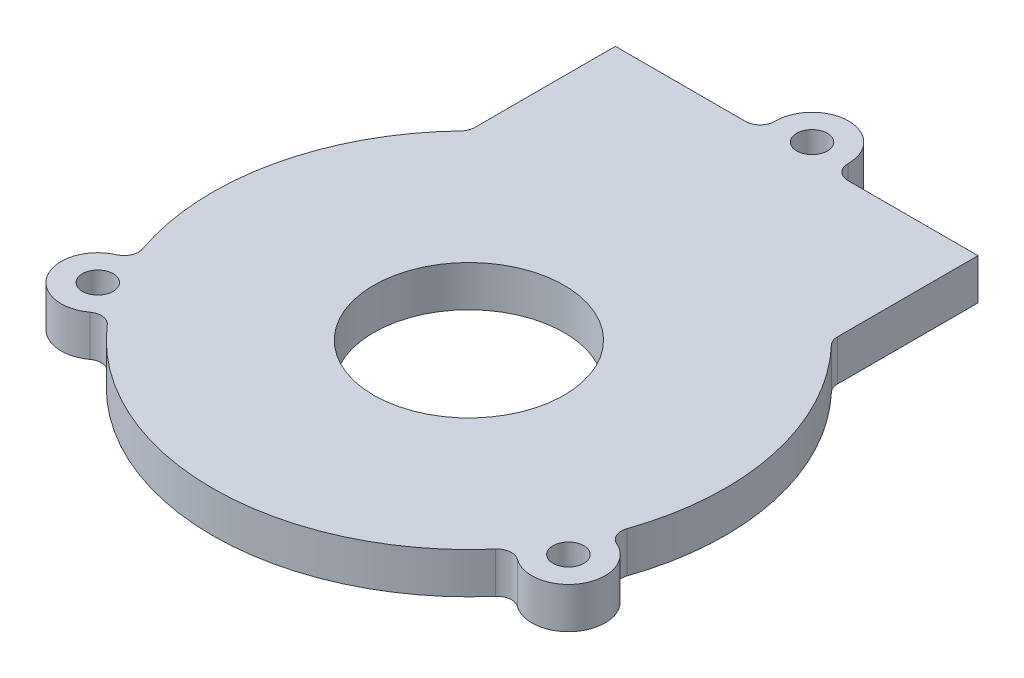
SolidWorks part; units mm, degrees
ref_plane "Front Plane" through (0, 0, 0) normal (0, 0, 1) x (1, 0, 0)
ref_plane "Top Plane" through (0, 0, 0) normal (0, 1, 0) x (1, 0, 0)
ref_plane "Right Plane" through (0, 0, 0) normal (1, 0, 0) x (0, 0, -1)
sketch "Sketch13" plane through (0, 0, 0) normal (0, 1, 0) x (1, 0, 0)
  circle A0 centre (0, 0) radius 35
extrude "Boss-Extrude3" add sketch "Sketch13" along normal blind 5.588
sketch "Sketch14" plane through (0, 5.588, 0) normal (0, 1, 0) x (1, 0, 0)
  line L0 (-24.7478, 24.7497) -> (24.7477, 24.7498)
  line L1 (-24.7478, 24.7497) -> (-24.7479, 44.7452)
  line L2 (24.7477, 24.7498) -> (24.7476, 44.7454)
  line L3 (-24.7479, 44.7452) -> (24.7476, 44.7454)
  line L4 (0, 0) -> (60.4611, -34.8658) construction
  line L5 (0, 0) -> (-56.6044, -32.6614) construction
  line L7 (-3.939, 44.1714) -> (-8.8985, 44.1714)
  line L8 (-3.939, 44.1714) -> (-3.939, 47.547)
  line L9 (-3.939, 47.547) -> (-8.8985, 47.547)
  line L10 (-8.8985, 44.1714) -> (-8.8985, 47.547)
  arc A0 (0, 35) -> (-24.7478, 24.7497) centre (0, 0) ccw construction
  circle A1 centre (0, 0) radius 35 construction
  arc A2 (0, 35) -> (-30.3109, -17.4999) centre (0, 0) ccw construction
  arc A3 (0, 35) -> (30.3118, -17.4984) centre (0, 0) ccw
  arc A4 (0, 35) -> (24.7477, 24.7498) centre (0, 0) ccw construction
  circle A5 centre (32.1365, -18.5413) radius 2.1017
  circle A6 centre (32.1365, -18.5413) radius 4.9951
  circle A7 centre (-32.1465, -18.5162) radius 2.0981
  circle A8 centre (-32.1465, -18.5162) radius 4.9995
extrude "Boss-Extrude4" add sketch "Sketch14" against normal up to surface (5.588 mm away) contours L0 L1 L3 L2 up to face at (0, 0, 35)
sketch "Sketch15" plane through (0, 5.588, 0) normal (0, 1, 0) x (1, 0, 0)
  line L0 (0, 0) -> (0, 62.3966) construction
  line L1 (-0.0001, 44.7453) -> (0, 46.8414) construction
  line L2 (-24.7479, 44.7452) -> (24.7476, 44.7454) construction
  circle A0 centre (0, 46.8414) radius 2.0961
  circle A1 centre (0, 46.8414) radius 4.996
extrude "Boss-Extrude11" add sketch "Sketch15" against normal up to surface (5.588 mm away) contours A1 | A0 up to face at (-0.0001, 0, -19.8101)
extrude "Boss-Extrude12" add sketch "Sketch14<6>" against normal up to surface (5.588 mm away) contours A6 up to face at (0, 0, -29.3038)
sketch "Sketch14<6>" plane through (0, 5.588, 0) normal (0, 1, 0) x (1, 0, 0) same geometry as "Sketch14"
extrude "Boss-Extrude14" add sketch "Sketch14<8>" against normal up to surface (5.588 mm away) contours L0 A5 region at (32.1365, 5.588, 18.5413) up to face at (5.9749, 0, -21.2696)
sketch "Sketch14<8>" plane through (0, 5.588, 0) normal (0, 1, 0) x (1, 0, 0) same geometry as "Sketch14"
hole_wizard "Ø4.2 (4.2) Diameter Hole1" positions "Sketch22" profile "Sketch23" hole size "Ø4.2" standard "ANSI Metric" end condition through all
sketch "Sketch22" plane through (0, 5.588, 0) normal (0, 1, 0) x (1, 0, 0)
  point P0 (32.1248, -18.5356)
sketch "Sketch23" plane through (32.1248, 5.588, 18.5356) normal (1, 0, 0) x (0, 0, 1)
  line L0 (0, 0) -> (0, 5.588)
  line L1 (0, 5.588) -> (2.1, 5.588)
  line L2 (2.1, 5.588) -> (2.1, 0)
  line L5 (2.1, 0) -> (0, 0)
  line L11 (0, -6.35) -> (0, 107.95) construction
  dimension "Thru Hole Dia." = 4.2
  dimension "Thru Hole Depth" = 5.588
extrude "Boss-Extrude15" add sketch "Sketch14<11>" against normal up to surface (5.588 mm away) contours A8 up to face at (32.1248, 0, 20.6356)
sketch "Sketch14<11>" plane through (0, 5.588, 0) normal (0, 1, 0) x (1, 0, 0) same geometry as "Sketch14"
hole_wizard "Ø4.2 (4.2) Diameter Hole2" positions "Sketch26" profile "Sketch27" hole size "Ø4.2" standard "ANSI Metric" end condition through all
sketch "Sketch26" plane through (0, 5.588, 0) normal (0, 1, 0) x (1, 0, 0)
  point P0 (-32.148, -18.5088)
  point P2 (-32.148, -18.5088)
sketch "Sketch27" plane through (-32.148, 5.588, 18.5088) normal (1, 0, 0) x (0, 0, 1)
  line L0 (0, 0) -> (0, 5.588)
  line L1 (0, 5.588) -> (2.1, 5.588)
  line L2 (2.1, 5.588) -> (2.1, 0)
  line L5 (2.1, 0) -> (0, 0)
  line L11 (0, -6.35) -> (0, 107.95) construction
  dimension "Thru Hole Dia." = 4.2
  dimension "Thru Hole Depth" = 5.588
fillet "Fillet4" radius 2 1 edges at (-24.7478, 2.794, -24.7497)
fillet "Fillet6" radius 2 1 edges at (-32.2839, 2.794, 13.5185)
fillet "Fillet7" radius 2 1 edges at (-27.8924, 2.794, 21.1427)
fillet "Fillet8" radius 2 1 edges at (27.8812, 2.794, 21.1574)
fillet "Fillet9" radius 2 1 edges at (32.2715, 2.794, 13.548)
fillet "Fillet10" radius 2 1 edges at (24.7477, 2.794, -24.7498)
fillet "Fillet11" radius 2 1 edges at (4.535, 2.794, -44.7453)
fillet "Fillet12" radius 2 1 edges at (-4.535, 2.794, -44.7453)
sketch "Sketch28" plane through (0, 5.588, 0) normal (0, 1, 0) x (1, 0, 0)
  circle A0 centre (0, 0) radius 5
extrude "Cut-Extrude1" cut sketch "Sketch28" against normal up to surface (5.588 mm away) up to face at (-32.148, 0, 20.6088)
sketch "Sketch29" plane through (0, 5.588, 0) normal (0, 1, 0) x (1, 0, 0)
  circle A0 centre (0, 0) radius 13
extrude "Cut-Extrude2" cut sketch "Sketch29" against normal up to surface (5.588 mm away) up to face at (0, 0, 5)
